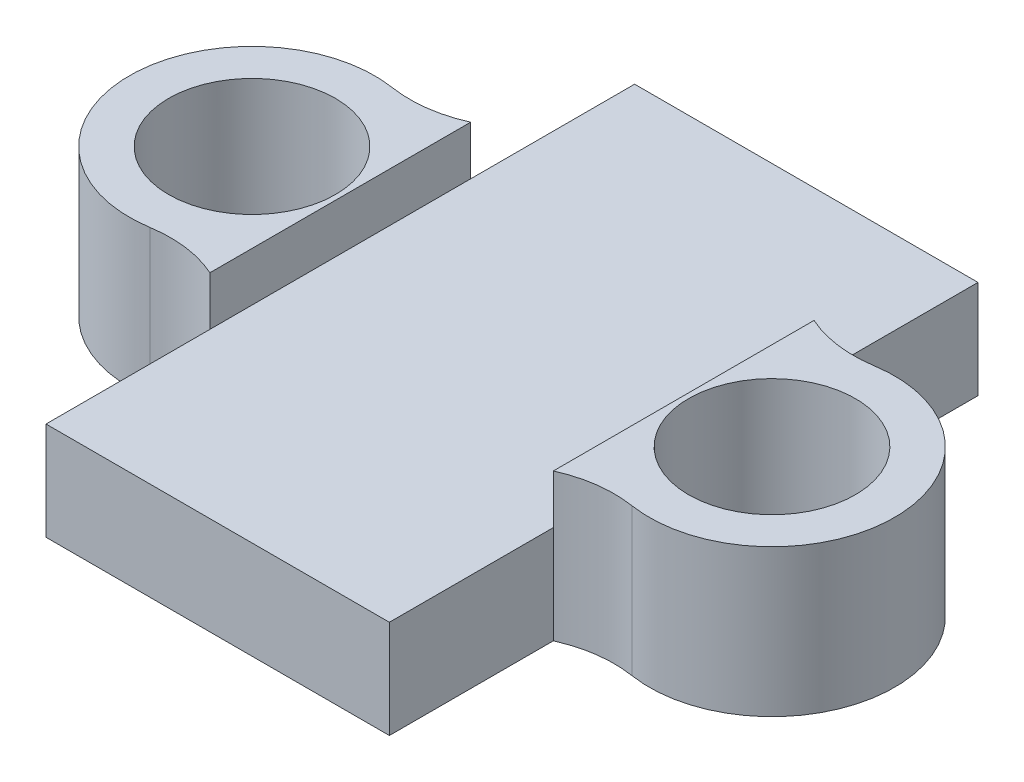
SolidWorks part; units mm, degrees
ref_plane "Alzado" through (0, 0, 0) normal (0, 0, 1) x (1, 0, 0)
ref_plane "Planta" through (0, 0, 0) normal (0, 1, 0) x (1, 0, 0)
ref_plane "Vista lateral" through (0, 0, 0) normal (1, 0, 0) x (0, 0, -1)
sketch "Croquis1" plane through (0, 0, 0) normal (0, 1, 0) x (1, 0, 0)
  line L0 (0, -16.4018) -> (0, 78.9163) construction
  line L1 (-63.9099, 0) -> (63.9099, 0) construction
  line L2 (-3.5, 6) -> (3.5, 6)
  line L3 (3.5, 6) -> (3.5, 2.6575)
  line L4 (-3.5, -6) -> (3.5, -6)
  line L5 (3.5, -6) -> (3.5, -2.6575)
  line L6 (-3.5, -6) -> (-3.5, -2.6575)
  line L7 (-3.5, 6) -> (-3.5, 2.6575)
  circle A0 centre (5.3, 0) radius 1.7
  arc A1 (4.911, -2.4695) -> (4.911, 2.4695) centre (5.3, 0) ccw
  arc A2 (3.5, 2.6575) -> (4.911, 2.4695) centre (4.5219, 4.9391) ccw
  arc A3 (3.5, -2.6575) -> (4.911, -2.4695) centre (4.5219, -4.9391) cw
  arc A4 (-3.5, -2.6575) -> (-4.911, -2.4695) centre (-4.5219, -4.9391) ccw
  arc A5 (-3.5, 2.6575) -> (-4.911, 2.4695) centre (-4.5219, 4.9391) cw
  arc A6 (-4.911, -2.4695) -> (-4.911, 2.4695) centre (-5.3, 0) cw
  circle A7 centre (-5.3, 0) radius 1.7
  point P6 (-7.8, 0)
  point P10 (7.8, 0)
  point P19 (0, 0)
  point P28 (0, -6)
  point P29 (-7.8, 0)
  point P30 (0, 6)
  point P31 (7.8, 0)
  dimension "D1" = 3.4
  dimension "D5" = 5
  dimension "D6" = 5
  dimension "D2" = 7.8
  dimension "D3" = 7.8
  dimension "D4" = 6
  dimension "D7" = 7
extrude "Saliente-Extruir1" add sketch "Croquis1" along normal blind 2
sketch "Croquis5" plane through (0, 2, 0) normal (0, 1, 0) x (1, 0, 0)
  line L0 (3.5, 2.6575) -> (3.5, -2.6575)
  line L1 (-3.5, -6) -> (3.5, -6) construction
  line L2 (3.5, 6) -> (-3.5, 6) construction
  line L3 (-3.5, -2.6575) -> (-3.5, 2.6575)
  line L7 (3.4556, 6) -> (3.5, 6)
  line L8 (3.5, -6) -> (3.5, -2.6575)
  line L9 (-3.5, -6) -> (3.5, -6)
  line L10 (3.5, -6) -> (3.5, -2.6575)
  line L11 (-3.5, -6) -> (3.5, -6) construction
  line L12 (3.5, 2.6575) -> (3.5, 6)
  line L13 (3.5, 2.6575) -> (3.5, 6)
  line L14 (3.4556, -6) -> (3.5, -6)
  arc A0 (-3.5, 2.6575) -> (-4.911, 2.4695) centre (-4.5219, 4.9391) cw
  arc A1 (-3.5, -2.6575) -> (-4.911, -2.4695) centre (-4.5219, -4.9391) ccw
  arc A2 (-4.911, -2.4695) -> (-4.911, 2.4695) centre (-5.3, 0) cw
  circle A3 centre (-5.3, 0) radius 1.7
  arc A12 (3.5, 2.6575) -> (4.911, 2.4695) centre (4.5219, 4.9391) ccw
  arc A13 (4.911, -2.4695) -> (4.911, 2.4695) centre (5.3, 0) ccw
  arc A14 (4.911, -2.4695) -> (3.5, -2.6575) centre (4.5219, -4.9391) ccw
  arc A15 (3.5, 2.6575) -> (4.911, 2.4695) centre (4.5219, 4.9391) ccw
  arc A16 (4.911, -2.4695) -> (4.911, 2.4695) centre (5.3, 0) ccw
  arc A17 (4.911, -2.4695) -> (3.5, -2.6575) centre (4.5219, -4.9391) ccw
  circle A18 centre (5.3, 0) radius 1.7
  circle M7 centre (5.3, 0) radius 1.7
  arc M11 (-3.5, 2.6575) -> (-4.911, 2.4695) centre (-4.5219, 4.9391) cw
  arc M12 (-4.911, 2.4695) -> (-4.911, -2.4695) centre (-5.3, 0) ccw
  arc M13 (-4.911, -2.4695) -> (-3.5, -2.6575) centre (-4.5219, -4.9391) cw
  arc M17 (3.5, -2.6575) -> (4.911, -2.4695) centre (4.5219, -4.9391) cw
  arc M18 (4.911, -2.4695) -> (4.911, 2.4695) centre (5.3, 0) ccw
  arc M19 (4.911, 2.4695) -> (3.5, 2.6575) centre (4.5219, 4.9391) cw
  circle M20 centre (-5.3, 0) radius 1.7
  dimension "D2" = 0
  dimension "D3" = 0
extrude "Boss-Extrude1" add sketch "Croquis5" along normal blind 1 contours M17 M18 M19 M7 | L3 M13 M11 M12 M20 region at (4.1828, 2, -2.3932) region at (-4.1828, 2, 2.3932)
